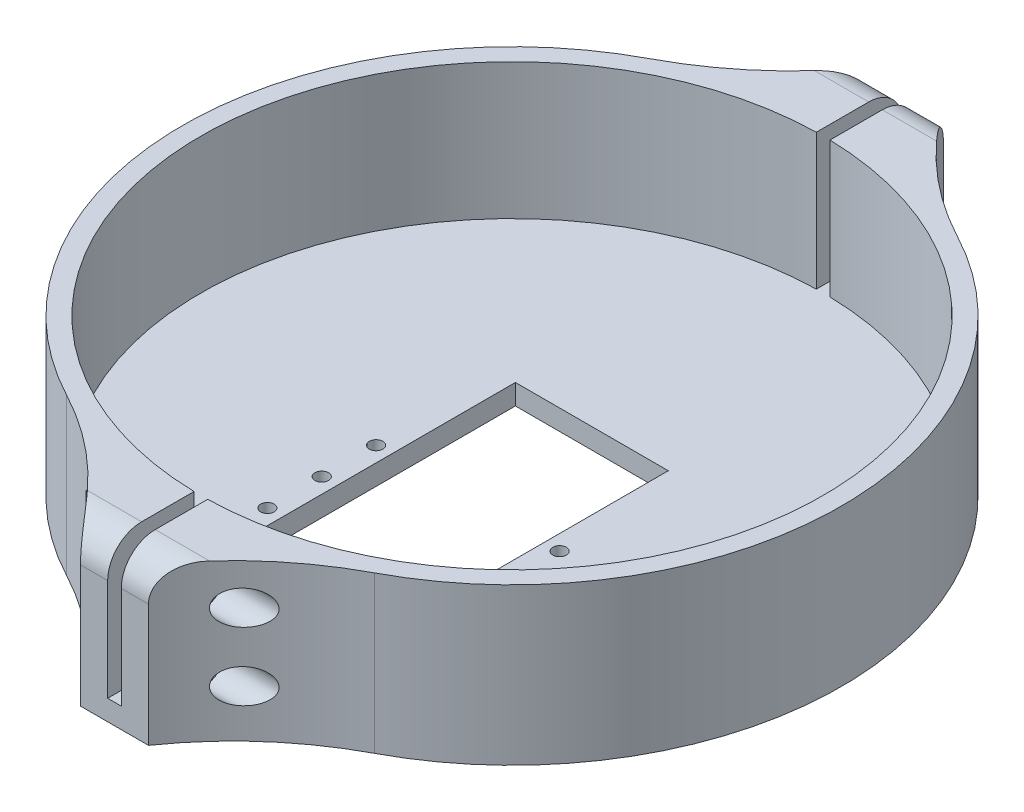
SolidWorks part; units mm, degrees
ref_plane "Front Plane" through (0, 0, 0) normal (0, 0, 1) x (1, 0, 0)
ref_plane "Top Plane" through (0, 0, 0) normal (0, 1, 0) x (1, 0, 0)
ref_plane "Right Plane" through (0, 0, 0) normal (1, 0, 0) x (0, 0, -1)
sketch "Sketch1" plane through (0, 0, 0) normal (0, 1, 0) x (1, 0, 0)
  circle A0 centre (0, 0) radius 45.8
  circle A1 centre (0, 0) radius 48.5
  dimension "D1" = 91.6
  dimension "D2" = 97
extrude "Boss-Extrude1" add sketch "Sketch1" along normal blind 20
sketch "Sketch2" plane through (0, 0, 0) normal (0, -1, 0) x (1, 0, 0)
  circle A0 centre (0, 0) radius 48.5
extrude "Boss-Extrude2" add sketch "Sketch2" along normal blind 3
sketch "Sketch5" plane through (0, 0, 0) normal (1, 0, 0) x (0, 0, -1)
  line L1 (-58.5, 20) -> (58.5, 20)
  line L2 (-58.5, 20) -> (-58.5, -3)
  line L3 (-58.5, -3) -> (58.5, -3)
  line L4 (58.5, 20) -> (58.5, -3)
  line L5 (-48.5, 20) -> (-48.5, -3) construction
  line L6 (48.5, -3) -> (48.5, 20) construction
  line L7 (48.5, 20) -> (-48.5, 20) construction
  dimension "D1" = 23
  dimension "D2" = 10
  dimension "D3" = 10
extrude "Boss-Extrude5" add sketch "Sketch5" along normal mid plane 10
sketch "Sketch6" plane through (0, 20, 0) normal (0, 1, 0) x (1, 0, 0)
  line L0 (5, 58.5) -> (-5, 58.5) construction
  line L1 (-1, 58.5) -> (1, 58.5)
  line L2 (-1, 58.5) -> (-1, 45.7891)
  line L3 (-1, -58.5) -> (1, -58.5)
  line L4 (1, 58.5) -> (1, 45.7891)
  line L5 (5, -58.5) -> (-5, -58.5) construction
  line L6 (5, 58.5) -> (5, 48.2416) construction
  line L7 (-1, -45.7891) -> (-1, -58.5)
  line L8 (1, -45.7891) -> (1, -58.5)
  arc A0 (-1, 45.7891) -> (-1, -45.7891) centre (0, 0) ccw
  arc A1 (1, -45.7891) -> (1, 45.7891) centre (0, 0) ccw
  dimension "D1" = 2
  dimension "D2" = 4
extrude "Cut-Extrude2" cut sketch "Sketch6" against normal up to surface (20 mm away) up to face at (-25.4, 0, 0)
fillet "Fillet1" radius 50 4 edges at (5, 8.5, 48.2416) (-5, 8.5, 48.2416) (5, 8.5, -48.2416) (-5, 8.5, -48.2416)
sketch "Sketch3" plane through (0, 0, 0) normal (0, 1, 0) x (1, 0, 0)
  line L1 (-11.25, 11.75) -> (11.25, 11.75)
  line L2 (-11.25, 11.75) -> (-11.25, -32.75)
  line L3 (-11.25, -32.75) -> (11.25, -32.75)
  line L4 (11.25, 11.75) -> (11.25, -32.75)
  dimension "D1" = 22.5
  dimension "D2" = 44.5
  dimension "D3" = 11.25
  dimension "D4" = 11.75
extrude "Cut-Extrude1" cut sketch "Sketch3" against normal up to surface (3 mm away) up to face at (0, -3, 0)
fillet "Fillet2" radius 5 4 edges at (-3, 20, -58.5) (3, 20, 58.5) (-3, 20, 58.5) (3, 20, -58.5)
sketch "Sketch7" plane through (0, 0, 0) normal (1, 0, 0) x (0, 0, -1)
  line L0 (58.5, -3) -> (58.5, 15) construction
  line L1 (53.5, 20) -> (42.8809, 20) construction
  line L2 (0, 0) -> (0, 25.0779) construction
  circle A0 centre (51, 14) radius 1.5
  circle A1 centre (51, 4) radius 1.5
  circle A2 centre (-51, 14) radius 1.5
  circle A3 centre (-51, 4) radius 1.5
  dimension "D2" = 3
  dimension "D3" = 3
  dimension "D1" = 7.5
  dimension "D4" = 6
  dimension "D5" = 10
extrude "Cut-Extrude3" cut sketch "Sketch7" against normal mid plane 81
ref_plane "Plane1" through (-16, 0, 0) normal (1, 0, 0) x (0, 0, -1)
sketch "Sketch8" plane through (-16, 0, 0) normal (1, 0, 0) x (0, 0, -1)
  circle A0 centre (51, 14) radius 2.5
  circle A1 centre (51, 4) radius 2.5
  dimension "D1" = 5
  dimension "D2" = 5
extrude "Cut-Extrude4" cut sketch "Sketch8" along normal blind 10
mirror "Mirror1" about plane through (0, 0, 0) normal (1, 0, 0) of "Cut-Extrude4"
mirror "Mirror2" about plane through (0, 0, 0) normal (0, 0, 1) of "Mirror1", "Cut-Extrude4"
sketch "Sketch9" plane through (0, 0, 0) normal (0, 1, 0) x (1, 0, 0)
  line L0 (0, 7.4603) -> (0, -43.0922) construction
  circle A1 centre (13.5, -6.5) radius 1
  circle A2 centre (13.5, -14.5) radius 1
  circle A3 centre (13.5, -22.5) radius 1
  circle A4 centre (13.5, -30.5) radius 1
  circle A5 centre (8, -36) radius 1
  circle A6 centre (-8, -36) radius 1
  circle A7 centre (-13.5, -30.5) radius 1
  circle A8 centre (-13.5, -22.5) radius 1
  circle A9 centre (-13.5, -14.5) radius 1
  circle A10 centre (-13.5, -6.5) radius 1
  dimension "D8" = 2
  dimension "D9" = 2
  dimension "D10" = 2
  dimension "D11" = 2
  dimension "D12" = 2
  dimension "D1" = 6.5
  dimension "D2" = 8
  dimension "D3" = 24
  dimension "D4" = 8
  dimension "D5" = 8
  dimension "D6" = 8
  dimension "D7" = 36
  dimension "D13" = 13.5
extrude "Cut-Extrude5" cut sketch "Sketch9" against normal up to surface (3 mm away) up to face at (0, -3, 10.5)
